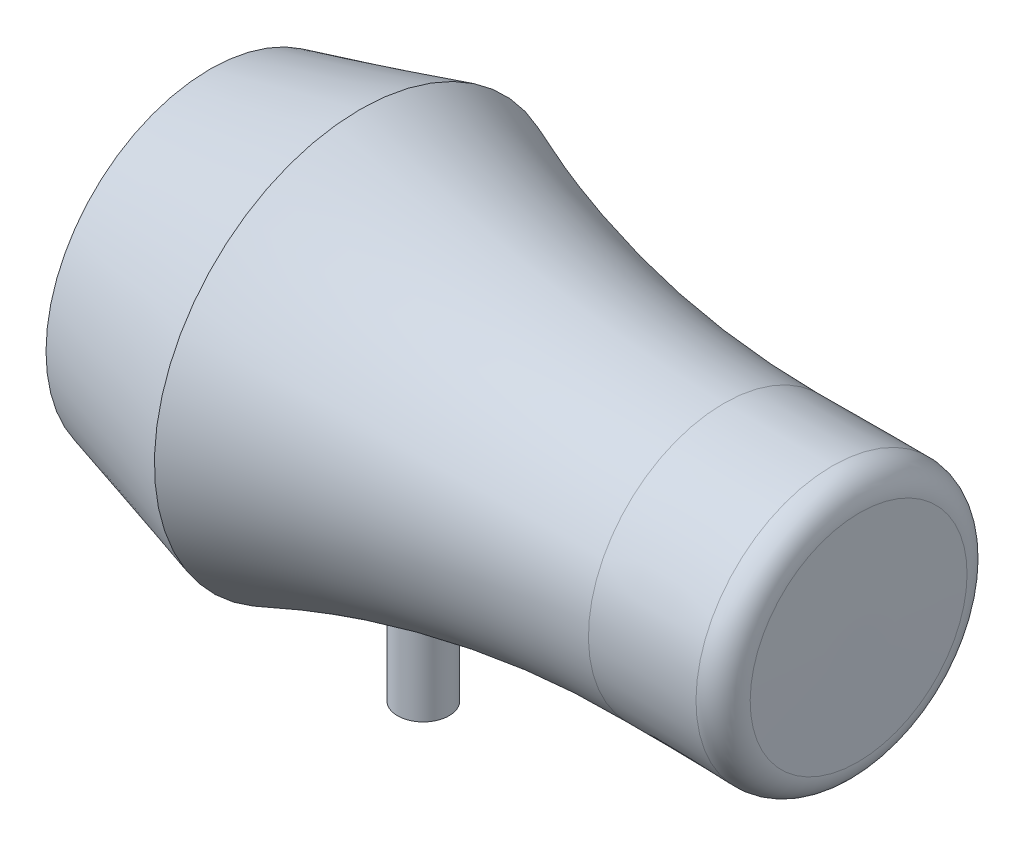
SolidWorks part; units mm, degrees
ref_plane "Front Plane" through (0, 0, 0) normal (0, 0, 1) x (1, 0, 0)
ref_plane "Top Plane" through (0, 0, 0) normal (0, 1, 0) x (1, 0, 0)
ref_plane "Right Plane" through (0, 0, 0) normal (1, 0, 0) x (0, 0, -1)
sketch "Sketch1" plane through (0, 0, 0) normal (0, 0, 1) x (1, 0, 0)
  line L5 (45.5246, -0.9769) -> (45.5246, 24.4231)
  line L7 (-50.8, 38.1) -> (-48.26, 38.1)
  line L8 (45.5246, 24.4231) -> (20.1246, 24.4231)
  line L13 (45.5246, -0.9769) -> (-76.2, 0)
  line L15 (-76.2, 0) -> (-76.2, 38.1)
  line L16 (-76.2, 38.1) -> (-50.8, 38.1)
  arc A1 (20.1246, 24.4231) -> (-48.26, 38.1) centre (20.1246, 202.2231) cw
  point P3 (0, 0)
  dimension "D1" = 177.8
  dimension "D2" = 25.4
  dimension "D4" = 2.54
  dimension "D5" = 25.4
revolve "Revolve2" add sketch "Sketch1" angle 360 about L13
fillet "Fillet2" radius 5.08 1 edges at (45.5246, 24.4231, 0)
chamfer "Chamfer1" distance 7.62 angle 75 1 edges at (-76.2, 38.1, 0)
ref_plane "Plane1" through (-76.2, 0, 0) normal (1, 0, 0) x (0, 0, -1)
sketch "Sketch3" plane through (-76.2, 0, 0) normal (1, 0, 0) x (0, 0, -1)
  circle A0 centre (0, 0) radius 4.826
  dimension "D1" = 9.652
extrude "Boss-Extrude1" add sketch "Sketch3" along normal mid plane 25.4
ref_plane "Plane2" through (0, -39.37, 0) normal (0, 1, 0) x (1, 0, 0)
sketch "Sketch5" plane through (0, -39.37, 0) normal (0, 1, 0) x (1, 0, 0)
  circle A0 centre (-36.2169, 0) radius 4.826
  dimension "D1" = 9.652
extrude "Boss-Extrude2" add sketch "Sketch5" along normal mid plane 25.4
